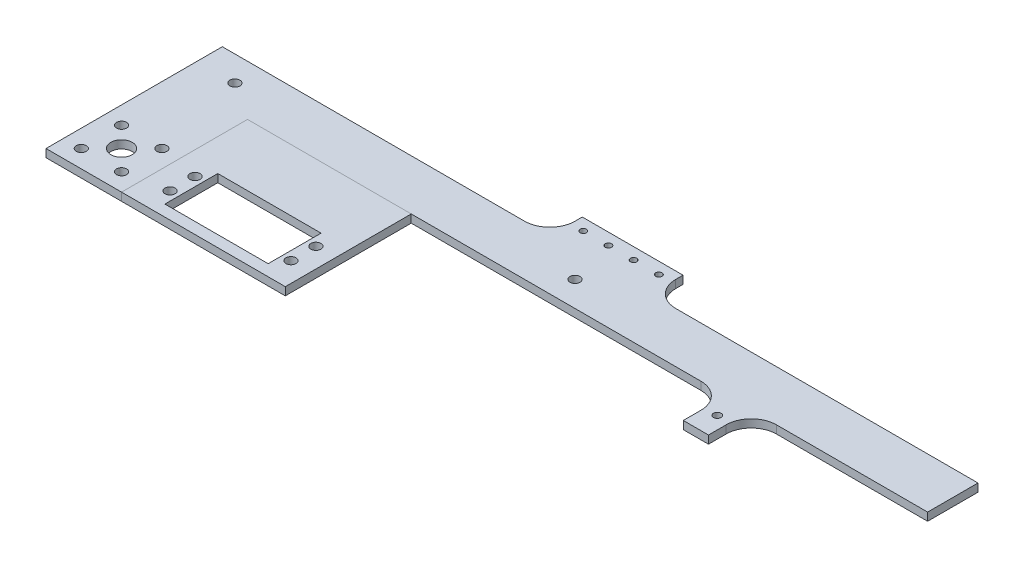
SolidWorks part; units mm, degrees
ref_plane "Front" through (0, 0, 0) normal (0, 0, 1) x (1, 0, 0)
ref_plane "Top" through (0, 0, 0) normal (0, 1, 0) x (1, 0, 0)
ref_plane "Right" through (0, 0, 0) normal (1, 0, 0) x (0, 0, -1)
sketch "Sketch1" plane through (0, 0, 0) normal (0, 1, 0) x (1, 0, 0)
  line L0 (225, -17) -> (225, -8.5)
  line L1 (0, 0) -> (230, 0)
  line L2 (0, 0) -> (0, 20)
  line L3 (0, 20) -> (230, 20)
  line L4 (230, 0) -> (230, 20)
  line L5 (230, 0) -> (220, 0)
  line L6 (230, 0) -> (230, -17)
  line L7 (230, -17) -> (220, -17)
  line L8 (220, 0) -> (220, -17)
  line L9 (165, 36.6) -> (165, 28.3)
  line L10 (170, 20) -> (160, 20)
  line L11 (170, 20) -> (170, 36.6)
  line L12 (170, 36.6) -> (160, 36.6)
  line L13 (160, 20) -> (160, 36.6)
  line L14 (230, 10) -> (150, 10)
  line L15 (150, 10) -> (15, 10)
  line L16 (15, 70) -> (15, 55)
  line L17 (30, 20) -> (0, 20)
  line L18 (30, 20) -> (30, 70)
  line L19 (30, 70) -> (0, 70)
  line L20 (0, 20) -> (0, 70)
  line L21 (15, 55) -> (7, 63)
  line L22 (160, 36.6) -> (130, 36.6)
  line L23 (130, 36.6) -> (130, 20)
  line L24 (30, 0) -> (30, -50)
  line L25 (30, -50) -> (0, -50)
  line L26 (0, 0) -> (0, -50)
  circle A0 centre (225, -8.5) radius 1.5
  circle A1 centre (165, 28.3) radius 1.25
  circle A2 centre (150, 10) radius 2
  circle A3 centre (15, 10) radius 2
  circle A4 centre (7, 63) radius 2
  circle A8 centre (15, 55) radius 4.25
  circle A9 centre (7, 47) radius 2
  circle A10 centre (23, 47) radius 2
  circle A11 centre (23, 63) radius 2
  circle A12 centre (155, 28.3) radius 1.25
  circle A13 centre (145, 28.3) radius 1.25
  circle A14 centre (135, 28.3) radius 1.25
  circle A15 centre (15, -35) radius 4.25
  circle A16 centre (7, -27) radius 2
  circle A17 centre (7, -43) radius 2
  circle A18 centre (23, -43) radius 2
  circle A19 centre (23, -27) radius 2
  point P40 (130, 55)
  dimension "D5" = 8.5
  dimension "D9" = 8.3
  dimension "D11" = 135
  dimension "D12" = 50
  dimension "D16" = 16
  dimension "D17" = 200
  dimension "D21" = 30
  dimension "D23" = 35
  dimension "D1" = 230
  dimension "D2" = 20
  dimension "D3" = 17
  dimension "D4" = 10
  dimension "D6" = 60
  dimension "D7" = 16.6
  dimension "D8" = 10
  dimension "D10" = 80
  dimension "D13" = 30
  dimension "D14" = 15
  dimension "D15" = 11.3137
  dimension "D18" = 16
  dimension "D19" = 0
  dimension "D20" = 16
  dimension "D22" = 4
extrude "Boss-Extrude1" add sketch "Sketch1" along normal blind 3.175 contours A3 A2 L4 L3 L2 L1 | A1 L12 L13 L3 L11 | L22 L23 L3 L13 A14 A13 A12 | A0 L7 L6 L1 L8 | L1 L26 L25 L24 A18 A16 A15 A17 A19 region at (222.5, 0, 16.8028) region at (225, 0, -2.3087) region at (15, 0, 24.2318) region at (165, 0, -20.1938) region at (145, 0, -20.3429)
fillet "Fillet1" radius 10 3 edges at (220, 1.5875, 0) (170, 1.5875, -20) (130, 1.5875, -20)
sketch "Sketch2" plane through (0, 0, 0) normal (0, -1, 0) x (-1, 0, 0)
  line L0 (-230, 20) -> (-230, 0)
  line L1 (-230, 20) -> (-300, 20)
  line L2 (-230, 0) -> (-300, 0)
  line L3 (-300, 20) -> (-300, 0)
  line L4 (-230, -17) -> (-230, 20) construction
  line L5 (-230, 10) -> (-285, 10)
  circle A0 centre (-285, 10) radius 2
  circle A1 centre (-150, 10) radius 2 construction
  dimension "D2" = 135
  dimension "D1" = 70
extrude "Boss-Extrude2" add sketch "Sketch2" against normal blind 3.175 contours L2 L3 L1 L0
fillet "Fillet2" radius 10 1 edges at (230, 1.5875, 0)
sketch "Sketch3" plane through (0, 0, 0) normal (0, -1, 0) x (-1, 0, 0)
  line L0 (-170, 30) -> (-170, 36.6) construction
  line L1 (-130, 36.6) -> (-170, 36.6)
  line L2 (-130, 36.6) -> (-130, 32.9)
  line L3 (-130, 32.9) -> (-170, 32.9)
  line L4 (-170, 36.6) -> (-170, 32.9)
  dimension "D1" = 3.7
extrude "Cut-Extrude1" cut sketch "Sketch3" against normal blind 10
sketch "Sketch4" plane through (0, 0, 0) normal (0, -1, 0) x (-1, 0, 0)
  line L0 (-30, -50) -> (-95, -50)
  line L1 (-95, -50) -> (-95, 0)
  line L2 (-30, 0) -> (-210, 0) construction
  line L5 (-15, -35) -> (-53.4, -35)
  line L6 (-53.4, -35) -> (-39.2, -35)
  line L7 (-39.2, -30.05) -> (-39.2, -39.95)
  line L8 (-39.2, -30.05) -> (-87.2, -30.05)
  line L9 (-87.2, -30.05) -> (-87.2, -39.95)
  line L10 (-39.2, -35) -> (-87.2, -35)
  line L11 (-30, -50) -> (-30, 0)
  line L12 (-42.7, -24.5) -> (-83.7, -24.5)
  line L13 (-42.7, -24.5) -> (-42.7, -45.5)
  line L14 (-42.7, -45.5) -> (-83.7, -45.5)
  line L15 (-83.7, -24.5) -> (-83.7, -45.5)
  line L16 (-42.7, -24.5) -> (-83.7, -45.5) construction
  line L17 (-42.7, -45.5) -> (-83.7, -24.5) construction
  line L18 (-30, 0) -> (-95, 0)
  circle A0 centre (-39.2, -30.05) radius 2
  circle A1 centre (-39.2, -39.95) radius 2
  circle A2 centre (-87.2, -39.95) radius 2
  circle A3 centre (-87.2, -30.05) radius 2
  point P15 (-39.2, -35)
  point P21 (-63.2, -35)
  line M14 (-210, 0) -> (-30, 0)
  line M15 (-30, 0) -> (-30, -50)
  dimension "D6" = 41
  dimension "D1" = 38.4
  dimension "D2" = 14.2
  dimension "D3" = 9.9
  dimension "D4" = 48
  dimension "D5" = 65
  dimension "D7" = 21
extrude "Boss-Extrude3" add sketch "Sketch4" against normal blind 3.175 separate body contours A3 L8 L15 L12 L13 A0 L7 L1 L0 A1 L5 L14 L10 A2 L9 M15 M14 | A0 L8 L13 L5 L7 | A3 L9 L10 L15 L8 region at (41.1496, 0, 32.8852) region at (62.2153, 0, 20.9589) region at (85.2504, 0, 32.8852)
